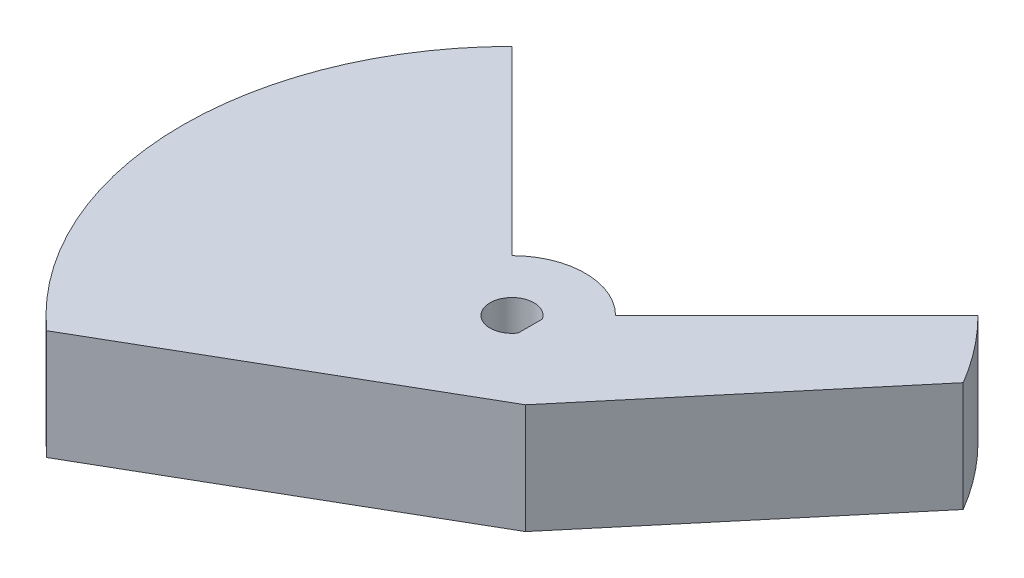
SolidWorks part; units mm, degrees
material "ABS"
ref_plane "Front Plane" through (0, 0, 0) normal (0, 0, 1) x (1, 0, 0)
ref_plane "Top Plane" through (0, 0, 0) normal (0, 1, 0) x (1, 0, 0)
ref_plane "Right Plane" through (0, 0, 0) normal (1, 0, 0) x (0, 0, -1)
sketch "Sketch1" plane through (0, 0, 0) normal (0, 1, 0) x (1, 0, 0)
  line L0 (-31.8198, 31.8198) -> (-7.0711, 7.0711)
  line L1 (7.0711, 7.0711) -> (31.8198, 31.8198)
  line L2 (0, 0) -> (0, 20) construction
  line L3 (0, 0) -> (-7.0711, 7.0711) construction
  line L4 (7.0711, 7.0711) -> (0, 0) construction
  arc A0 (-31.8198, 31.8198) -> (31.8198, 31.8198) centre (0, 0) ccw
  circle A1 centre (0, 0) radius 3
  arc A2 (7.0711, 7.0711) -> (-7.0711, 7.0711) centre (0, 0) ccw
  dimension "D1" = 6
  dimension "D2" = 90
  dimension "D3" = 20
  dimension "D4" = 45
extrude "Boss-Extrude1" add sketch "Sketch1" along normal blind 15
sketch "Sketch2" plane through (0, 15, 0) normal (0, 1, 0) x (1, 0, 0)
  line L0 (2.5, 1.6583) -> (2.5, -1.6583)
  line L1 (-3, 0) -> (-3, -6.6376) construction
  arc A0 (2.5, -1.6583) -> (2.5, 1.6583) centre (0, 0) ccw
  circle A1 centre (0, 0) radius 3 construction
  dimension "D1" = 5.5
extrude "Shaft D" add sketch "Sketch2" against normal up to surface (15 mm away) up to face at (0, 0, -0.9727)
sketch "Sketch3" plane through (0, 15, 0) normal (0, 1, 0) x (1, 0, 0)
  line L0 (-31.8198, 31.8198) -> (-27.5772, 36.0624)
  line L1 (-27.5772, 36.0624) -> (-27.5772, 27.5772)
  line L2 (-7.0711, 7.0711) -> (-31.8198, 31.8198) construction
  line L3 (-27.5772, 27.5772) -> (-31.8198, 31.8198)
  line L4 (0, 0) -> (0, 30.6174) construction
  line L5 (27.5772, 27.5772) -> (31.8198, 31.8198)
  line L6 (27.5772, 36.0624) -> (27.5772, 27.5772)
  line L7 (31.8198, 31.8198) -> (27.5772, 36.0624)
  dimension "D1" = 6
extrude "Boss-Extrude2" [suppressed] add sketch "Sketch3" against normal up to surface (15 mm away) up to face at (0, 0, -0.9727)
sketch "Sketch4" plane through (0, 15, 0) normal (0, 1, 0) x (1, 0, 0)
  line L0 (-148.943, 0) -> (142.5774, 0) construction
  line L1 (0, 0) -> (-107.5774, -62.1099) construction
  line L2 (0, 0) -> (49.4281, -41.4751) construction
  line L8 (0, 0) -> (41.4751, 49.4281) construction
  line L9 (0, 0) -> (62.1099, -107.5774) construction
  line L10 (-107.5774, -62.1099) -> (62.1099, -107.5774) construction
  line L11 (41.4751, 49.4281) -> (49.4281, -41.4751) construction
  line L14 (11.4907, -9.6418) -> (45.5038, 30.8934)
  line L15 (11.4907, -9.6418) -> (-38.9929, -38.7885)
  arc A2 (-38.9929, -38.7885) -> (45.5038, 30.8934) centre (0, 0) ccw
  dimension "D4" = 55
  dimension "D1" = 40
  dimension "D3" = 30
  dimension "D5" = 15
extrude "Cut-Extrude1" cut sketch "Sketch4" against normal through all
